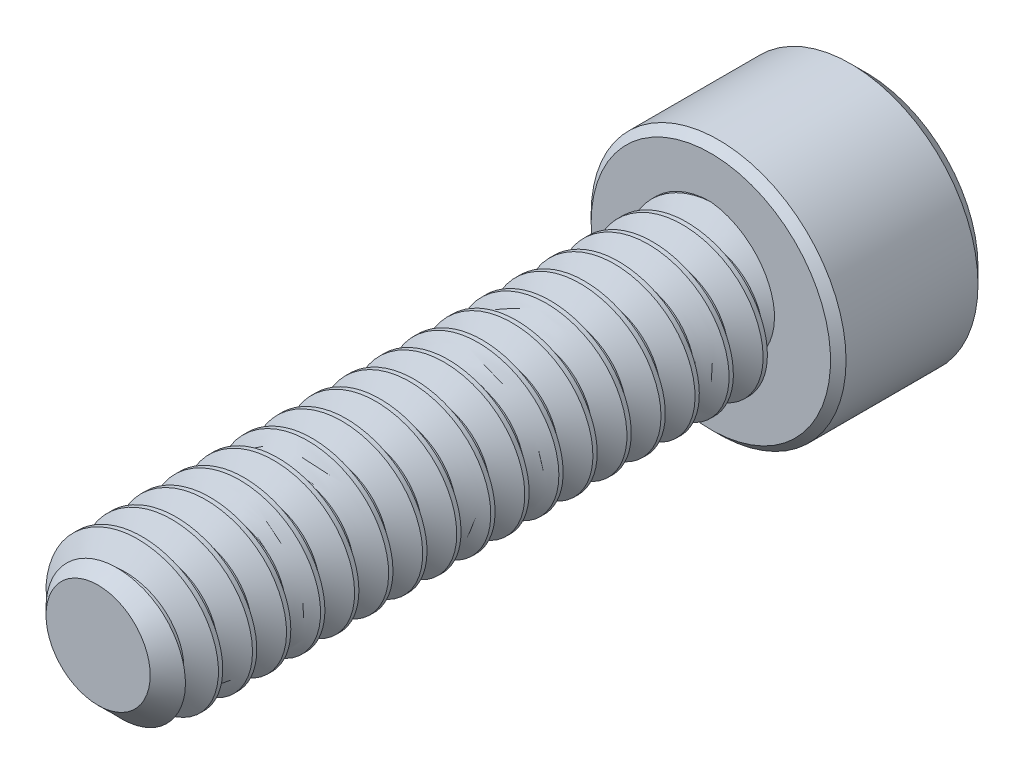
SolidWorks part; units mm, degrees
ref_plane "Front Plane" through (0, 0, 0) normal (0, 0, 1) x (1, 0, 0)
ref_plane "Top Plane" through (0, 0, 0) normal (0, 1, 0) x (1, 0, 0)
ref_plane "Right Plane" through (0, 0, 0) normal (1, 0, 0) x (0, 0, -1)
sketch "Sketch1" plane through (0, 0, 0) normal (0, 0, 1) x (1, 0, 0)
  line L0 (0, 2.413) -> (0, -2.413) construction
  circle A0 centre (0, 0) radius 2.413
  dimension "OD" = 4.826
extrude "Extrude1" add sketch "Sketch1" against normal blind 19.05
sketch "Sketch2" plane through (0, 0, 0) normal (0, 0, 1) x (1, 0, 0)
  circle A0 centre (0, 0) radius 2.413 construction
  circle A1 centre (0, 0) radius 2.413
curve "Helix/Spiral1" pitch 1.0583 height 20.1083 turns 19 parameters "pitch"=1.0583
chamfer "Chamfer3" distance 0.7937 angle 45 1 edges at (2.413, 0, 0)
sketch "Sketch3" plane through (0, 0, 0) normal (1, 0, 0) x (0, 0, -1)
  line L0 (-0.926, 2.413) -> (-0.5292, 1.7256)
  line L1 (-0.5292, 1.7256) -> (-0.3969, 1.7256)
  line L2 (-0.3969, 1.7256) -> (0, 2.413)
  line L3 (-0.926, 2.413) -> (0, 2.413)
  line L4 (-0.463, 2.413) -> (-0.463, 1.7256) construction
  line L5 (-0.7276, 2.0693) -> (-0.1984, 2.0693) construction
  line L6 (0, 2.413) -> (0, -2.413) construction
  dimension "D1" = 0.1323
  dimension "D2" = 0.5292
  dimension "D3" = 60
sweep "Cut-Sweep1" cut profiles "Sketch3" path "Helix/Spiral1"
sketch "Sketch6" plane through (0, 0, -19.05) normal (0, 0, -1) x (-1, 0, 0)
  circle A0 centre (0, 0) radius 3.9624
  dimension "head dia" = 7.9248
extrude "Extrude2" add sketch "Sketch6" along normal blind 4.826
sketch "Sketch7" plane through (0, 0, -23.876) normal (0, 0, -1) x (-1, 0, 0)
  line L1 (0, 2.2914) -> (-1.9844, 1.1457)
  line L2 (-1.9844, 1.1457) -> (-1.9844, -1.1457)
  line L3 (-1.9844, -1.1457) -> (0, -2.2914)
  line L4 (0, -2.2914) -> (1.9844, -1.1457)
  line L5 (1.9844, -1.1457) -> (1.9844, 1.1457)
  line L6 (1.9844, 1.1457) -> (0, 2.2914)
  circle A0 centre (0, 0) radius 1.9844 construction
  dimension "hex dia" = 3.9688
extrude "Cut-Extrude1" cut sketch "Sketch7" against normal blind 2.9766
sketch "Sketch8" plane through (0, 0, -23.876) normal (0, 0, -1) x (-1, 0, 0)
  circle A0 centre (0, 0) radius 2.2914
extrude "Cut-Extrude2" cut sketch "Sketch8" against normal blind 0.4826 draft 45
chamfer "Chamfer1" distance 0.4826 angle 45 1 edges at (-3.9624, 0, -23.876)
chamfer "Chamfer2" distance 0.2413 angle 45 1 edges at (-3.9624, 0, -19.05)
sketch "Sketch9" plane through (0, 0, 0) normal (1, 0, 0) x (0, 0, -1)
  line L0 (0, 2.413) -> (0, -2.413) construction
  line L1 (5.8208, 2.413) -> (5.8208, -2.413) construction
  line L2 (19.05, 3.9624) -> (19.05, -3.9624) construction
  line L3 (23.876, 3.9624) -> (23.876, -3.9624) construction
  line L4 (23.876, 0) -> (0, 0) construction
  dimension "D1" = 5.8208
  dimension "D2" = 4.826
  dimension "D3" = 7.9248
  dimension "D4" = 19.05
equation "\"D3@Helix/Spiral1\" = \"screw length@Extrude1\"+\"pitch@Helix/Spiral1\""
equation "\"D1@Sketch3\" = \"pitch@Helix/Spiral1\"*.125"
equation "\"D2@Sketch3\" = \"pitch@Helix/Spiral1\"*.5"
equation "\"D1@Cut-Extrude1\" = \"hex dia@Sketch7\"*.75"
equation "\"D1@Chamfer1\" = \"head depth@Extrude2\"/10"
equation "\"D1@Sketch9\" = \"pitch@Helix/Spiral1\"*5.5"
equation "\"D1@Chamfer2\" = \"D1@Chamfer1\"/2"
equation "\"D1@Cut-Extrude2\" = \"D1@Chamfer2\"*2"
equation "\"D1@Chamfer3\" = \"pitch@Helix/Spiral1\"*.750"
equation "\"D2@Sketch9\" = \"head depth@Extrude2\""
equation "\"D3@Sketch9\" = \"head dia@Sketch6\""
equation "\"D4@Sketch9\" = \"screw length@Extrude1\""
